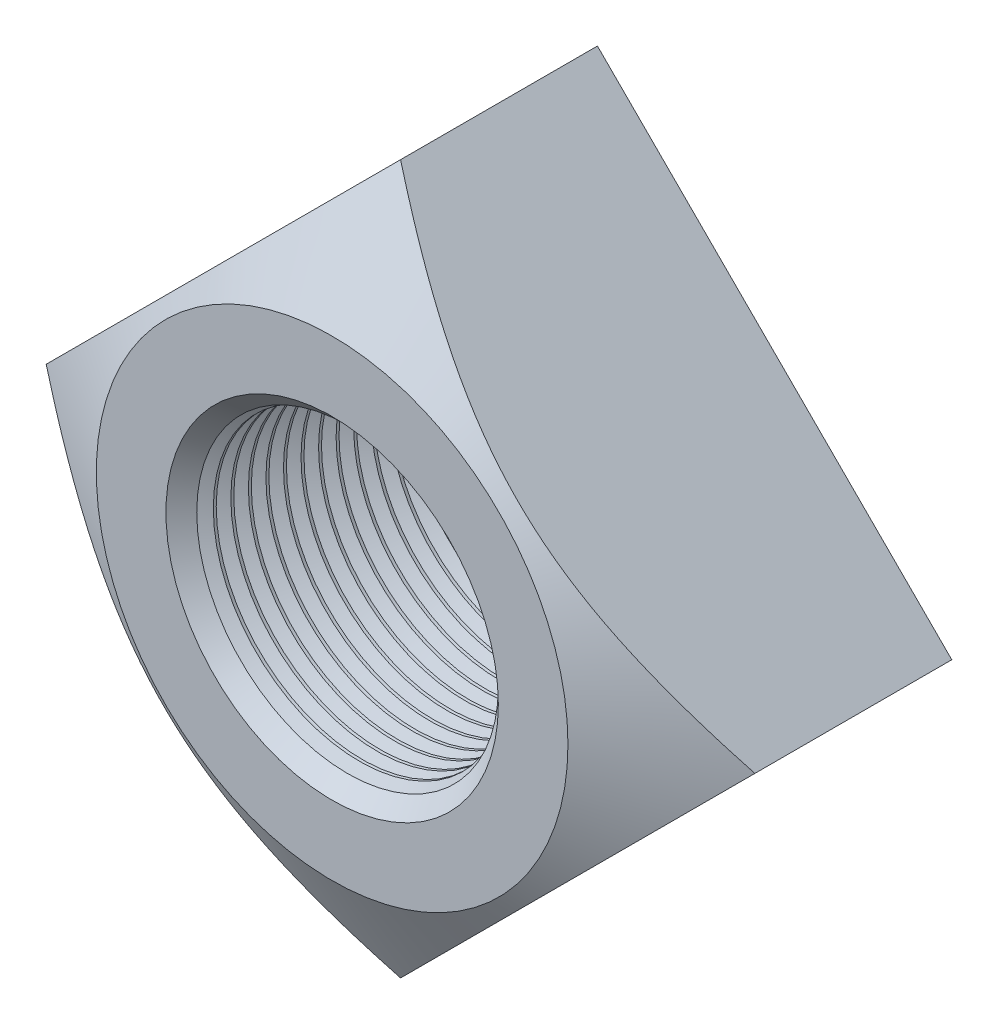
SolidWorks part; units mm, degrees
ref_plane "Front" through (0, 0, 0) normal (0, 0, 1) x (1, 0, 0)
ref_plane "Top" through (0, 0, 0) normal (0, 1, 0) x (1, 0, 0)
ref_plane "Right" through (0, 0, 0) normal (1, 0, 0) x (0, 0, -1)
sketch "Sketch1" plane through (0, 0, 0) normal (0, 0, 1) x (1, 0, 0)
  line L1 (0, 24.0416) -> (-24.0416, 0)
  line L2 (-24.0416, 0) -> (0, -24.0416)
  line L3 (0, -24.0416) -> (24.0416, 0)
  line L4 (24.0416, 0) -> (0, 24.0416)
  circle A0 centre (0, 0) radius 17 construction
  circle A1 centre (0, 0) radius 9.9175
  dimension "D1" = 19.835
extrude "BaseNut" add sketch "Sketch1" against normal blind 18
cosmetic thread "ThreadCosmetic1" [suppressed] parameters "D2"=22
sketch "Sketch2" plane through (0, 0, 0) normal (0, 1, 0) x (-1, 0, 0)
  line L0 (0, 6.7358) -> (0, -22.2595) construction
  line L2 (16, 0) -> (24.0416, 0)
  line L4 (24.0416, 0) -> (24.0416, -4.6428)
  line L6 (24.0416, -4.6428) -> (16, 0)
  dimension "D1" = 32
  dimension "D2" = 30
revolve "Single-Chamfer" cut sketch "Sketch2" angle 360 about L0
chamfer "Chamfer1" distance 1.36 angle 45 2 edges at (9.9175, 0, -18) (9.9175, 0, 0)
sketch "Sketch3" plane through (0, 0, 0) normal (0, 1, 0) x (1, 0, 0)
  line L0 (0, 25.6396) -> (0, -7.8226) construction
  line L1 (8.9258, 1.8559) -> (9.9175, 1.8559)
  line L2 (9.9175, 1.8559) -> (10.7764, 1.36)
  line L3 (10.7764, 1.36) -> (9.9175, 0.8641)
  line L4 (9.9175, 0.8641) -> (8.9258, 0.8641)
  line L5 (8.9258, 0.8641) -> (8.9258, 1.8559)
  line L6 (9.9175, 1.36) -> (-9.9175, 1.36) construction
  dimension "D1" = 0.9918
  dimension "D2" = 19.835
revolve "Cut-Revolve10" cut sketch "Sketch3" angle 360 about L0
pattern_linear "LPattern10" count 13 spacing 1.1901 along (0, 0, -1) of "Cut-Revolve10"
equation "\"D1@Sketch2\" = \"s@Sketch1\"-2"
equation "\"D1@Chamfer1\" = \"s@Sketch1\" / 25"
equation "\"D2@Sketch3\" = \"D1@Sketch1\""
equation "\"D1@Sketch3\" = ( \"D1@Sketch1\" )  / 20"
equation "\"D3@LPattern10\" = \"D1@Sketch3\" * 1.2"
equation "\"D1@LPattern10\" = (  \"m@BaseNut\" -  ( 2 * \"D1@Chamfer1\" )  )  / \"D3@LPattern10\""
